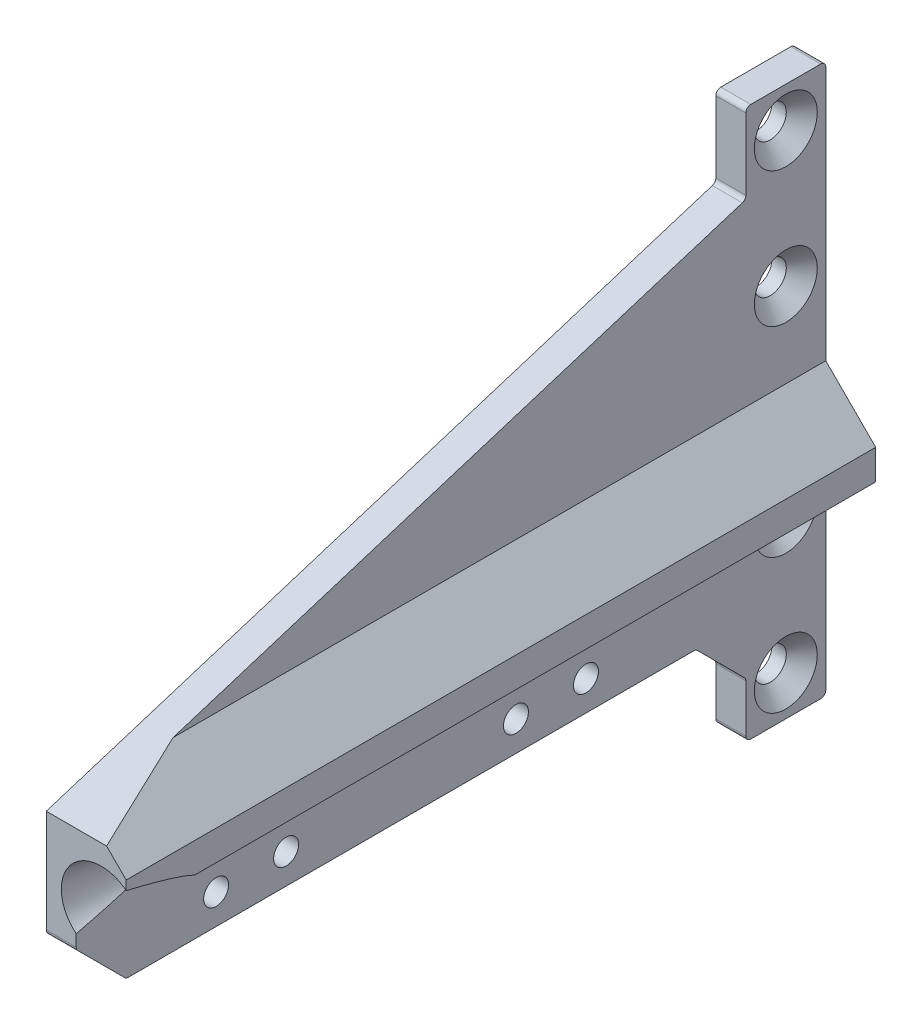
SolidWorks part; units mm, degrees
ref_plane "Front Plane" through (0, 0, 0) normal (0, 0, 1) x (1, 0, 0)
ref_plane "Top Plane" through (0, 0, 0) normal (0, 1, 0) x (1, 0, 0)
ref_plane "Right Plane" through (0, 0, 0) normal (1, 0, 0) x (0, 0, -1)
sketch "Sketch1" plane through (0, 0, 0) normal (0, 0, 1) x (1, 0, 0)
  line L0 (-736.1635, 0) -> (36072.0133, 0) construction
  line L1 (0, -736.1635) -> (0, 36072.0133) construction
  line L2 (25, 1.0355) -> (30, 1.0355) construction
  line L3 (0, 22) -> (22, 22) construction
  line L4 (0, 22) -> (0, -24.3053) construction
  line L5 (0, -24.3053) -> (22, -24.3053) construction
  line L6 (22, 22) -> (22, -24.3053) construction
  line L7 (22, -20) -> (25, -20)
  line L8 (22, -20) -> (22, 35)
  line L9 (22, 35) -> (25, 35)
  line L10 (25, -20) -> (25, 1.0355)
  line L11 (27.5, 3.5355) -> (25, 1.0355)
  line L12 (30, 1.0355) -> (30, 9.0355)
  line L13 (30, 9.0355) -> (25, 9.0355)
  line L14 (30, 1.0355) -> (27.5, 3.5355)
  line L15 (27.5, -3.5355) -> (29.2678, -1.7678) [skipped]
  line L16 (25, -1.0355) -> (25.7322, -1.7678) [skipped]
  line L17 (25, 9.0355) -> (25, 35)
  circle A0 centre (27.5, 0) radius 1.8404 construction
  circle A1 centre (27.5, 0) radius 2.5 construction
  dimension "D1" = 27.5
  dimension "D5" = 5
  dimension "D2" = 3
  dimension "D3" = 55
  dimension "D4" = 20
  dimension "D6" = 8
  dimension "D7" = 21.0355
extrude "Boss-Extrude1" add sketch "Sketch1" along normal blind 75
ref_axis "Axis1" through (27.5, 0, 0) along (0, 0, 1)
sketch "Sketch4" plane through (0, 0, 0) normal (0, 1, 0) x (1, 0, 0)
  line L0 (27.5, -67.0346) -> (30, -67.0346)
  line L1 (27.5, 0) -> (27.5, -76.1658) construction
  line L2 (30, -67.0346) -> (31.5, -75.0346)
  line L3 (31.5, -75.0346) -> (27.5, -75.0346)
  line L4 (27.5, -75.0346) -> (27.5, -67.0346)
  dimension "D1" = 4
  dimension "D2" = 2.5
  dimension "D3" = 8
revolve "Cut-Revolve1" cut sketch "Sketch4" angle 360 about axis through (27.5, 0, 0) along (0, 0, 1)
sketch "Sketch6" plane through (22, 0, 0) normal (-1, 0, 0) x (0, 0, 1)
  line L1 (75, 35) -> (0, 35) construction
  line L2 (75, 35) -> (75, -20) construction
  line L3 (75, 6) -> (75, 35)
  line L4 (75, 35) -> (8, 35)
  line L5 (0, -20) -> (0, 35) construction
  line L6 (0, 0) -> (76.1658, 0) construction
  line L7 (0, -20) -> (0, 1.0355) construction
  line L8 (75, -20) -> (8, -20)
  line L9 (75, -20) -> (75, -9.5)
  line L10 (75, -9.5) -> (8, -9.5)
  line L11 (8, -20) -> (8, -9.5)
  line L12 (8, 35) -> (8, 27)
  line L13 (8, 27) -> (75, 6)
  dimension "D1" = 8
  dimension "D2" = 6
  dimension "D3" = 9.5
  dimension "D4" = 8
  dimension "D5" = 8
extrude "Cut-Extrude3" cut sketch "Sketch6" against normal blind 55
chamfer "Chamfer3" distance 5 angle 45 2 edges at (23.5, -9.5, 8) (23.5, -9.5, 75)
chamfer "Chamfer4" distance 5 angle 45 1 edges at (30, 9.0355, 32.6576)
hole_wizard "CSK for M3 Flat Head Machine Screw1" positions "Sketch7" profile "Sketch8" countersink size "M3" standard "ANSI Metric" end condition through all
sketch "Sketch7" plane through (25, 0, 0) normal (1, 0, 0) x (0, 0, -1)
  line L0 (-8, 35) -> (0, 35) construction
  line L1 (0, -200736.1635) -> (0, 236072.0133) construction
  line L3 (-8, -20) -> (0, -20) construction
  point P0 (-4, 31)
  point P2 (-4, 17.5)
  point P4 (-4, -16)
  point P6 (-4, -2.5)
  dimension "D1" = 4
  dimension "D2" = 4
  dimension "D3" = 13.5
  dimension "D5" = 4
  dimension "D6" = 13.5
sketch "Sketch8" plane through (25, 31, 4) normal (0, 1, 0) x (0, 0, -1)
  line L0 (0, 0) -> (0, 3)
  line L1 (0, 3) -> (1.6, 3)
  line L2 (1.6, 3) -> (1.6, 1.55)
  line L3 (1.6, 1.55) -> (3.15, 0)
  line L5 (3.15, 0) -> (0, 0)
  line L6 (-1.6, 1.55) -> (-3.15, 0) construction
  line L11 (0, -6.35) -> (0, 107.95) construction
  dimension "Thru Hole Dia." = 3.2
  dimension "Thru Hole Depth" = 3
  dimension "Near C'Sink Dia." = 6.3
  dimension "Near C'Sink Angle" = 90
hole_wizard "Tap Drill for M3x0.5 Tap1" positions "Sketch9" profile "Sketch10" hole size "M3x0.5" standard "ANSI Metric" end condition through all
sketch "Sketch9" plane through (25, 0, 0) normal (1, 0, 0) x (0, 0, -1)
  line L0 (-75, -4.5) -> (-75, -3.1142) construction
  line L1 (-70, -9.5) -> (-13, -9.5) construction
  point P0 (-61, -6.5)
  point P2 (-54, -6.5)
  dimension "D1" = 7
  dimension "D2" = 14
  dimension "D3" = 3
sketch "Sketch10" plane through (25, -6.5, 61) normal (0, 1, 0) x (0, 0, -1)
  line L0 (0, 0) -> (0, 3)
  line L1 (0, 3) -> (1.25, 3)
  line L2 (1.25, 3) -> (1.25, 0)
  line L5 (1.25, 0) -> (0, 0)
  line L11 (0, -6.35) -> (0, 107.95) construction
  dimension "Thru Hole Dia." = 2.5
  dimension "Thru Hole Depth" = 3
hole_wizard "Tap Drill for M3x0.5 Tap2" positions "Sketch11" profile "Sketch12" hole size "M3x0.5" standard "ANSI Metric" end condition through all
sketch "Sketch11" plane through (25, 0, 0) normal (1, 0, 0) x (0, 0, -1)
  point P0 (-24, -6.5)
  point P3 (-31, -6.5)
sketch "Sketch12" plane through (25, -6.5, 24) normal (0, 1, 0) x (0, 0, -1)
  line L0 (0, 0) -> (0, 3)
  line L1 (0, 3) -> (1.25, 3)
  line L2 (1.25, 3) -> (1.25, 0)
  line L5 (1.25, 0) -> (0, 0)
  line L11 (0, -6.35) -> (0, 107.95) construction
  dimension "Thru Hole Dia." = 2.5
  dimension "Thru Hole Depth" = 3
fillet "Fillet1" radius 0.5 9 edges at (23.5, -4.5, 75) (23.5, -20, 0) (23.5, -9.5, 70) (23.5, -9.5, 13) (23.5, -14.5, 8) (23.5, -20, 8) (23.5, 35, 0) (23.5, 27, 8) (23.5, 35, 8)
